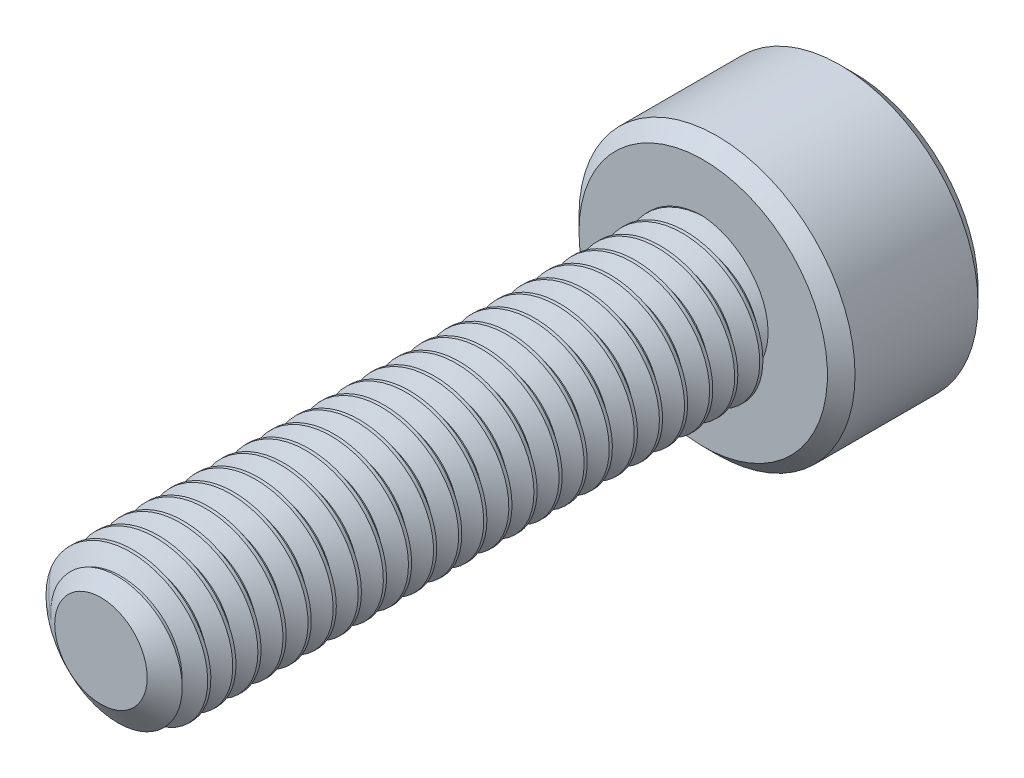
SolidWorks part; units mm, degrees
ref_plane "Front Plane" through (0, 0, 0) normal (0, 0, 1) x (1, 0, 0)
ref_plane "Top Plane" through (0, 0, 0) normal (0, 1, 0) x (1, 0, 0)
ref_plane "Right Plane" through (0, 0, 0) normal (1, 0, 0) x (0, 0, -1)
sketch "Sketch1" plane through (0, 0, 0) normal (0, 0, 1) x (1, 0, 0)
  circle A0 centre (0, 0) radius 1.5
  dimension "OD" = 3
extrude "Extrude1" add sketch "Sketch1" against normal blind 12
sketch "Sketch2" plane through (0, 0, 0) normal (0, 0, 1) x (1, 0, 0)
  circle A0 centre (0, 0) radius 1.5 construction
  circle A1 centre (0, 0) radius 1.5
curve "Helix/Spiral1" pitch 0.5 height 12.5 radius 1.5 centre (0, 0, 0) axis (0, 0, -1) start towards (0, 1, 0) parameters "pitch"=0.5
sketch "Sketch3" plane through (0, 0, 0) normal (1, 0, 0) x (0, 0, -1)
  line L0 (-0.4375, 1.5) -> (-0.25, 1.1752)
  line L1 (-0.25, 1.1752) -> (-0.1875, 1.1752)
  line L2 (-0.1875, 1.1752) -> (0, 1.5)
  line L3 (-0.4375, 1.5) -> (0, 1.5)
  line L4 (-0.2187, 1.5) -> (-0.2187, 1.1752) construction
  line L5 (-0.3438, 1.3376) -> (-0.0937, 1.3376) construction
  line L6 (0, 1.5) -> (0, -1.5) construction
  dimension "D1" = 0.0625
  dimension "D2" = 0.25
  dimension "D3" = 60
sweep "Cut-Sweep1" cut profiles "Sketch3" path "Helix/Spiral1" align with end faces yes
sketch "Sketch4" plane through (0, 0, 0) normal (1, 0, 0) x (0, 0, -1)
  line L0 (0.4053, 1.5) -> (0, 0.9212)
  line L1 (0, 0.9212) -> (0, 1.5)
  line L2 (0.4053, 1.5) -> (0, 1.5)
  line L3 (-0.4375, 1.5) -> (0, 1.5) construction
  line L4 (0, 0) -> (7.0209, 0) construction
  dimension "D1" = 55
  dimension "D2" = 0.254
revolve "Cut-Revolve1" cut sketch "Sketch4" angle 360 about L4
sketch "Sketch6" plane through (0, 0, -12) normal (0, 0, -1) x (-1, 0, 0)
  circle A0 centre (0, 0) radius 2.75
  dimension "head dia" = 5.5
extrude "Extrude2" add sketch "Sketch6" along normal blind 3
sketch "Sketch7" plane through (0, 0, -15) normal (0, 0, -1) x (-1, 0, 0)
  line L1 (0, 1.4434) -> (-1.25, 0.7217)
  line L2 (-1.25, 0.7217) -> (-1.25, -0.7217)
  line L3 (-1.25, -0.7217) -> (0, -1.4434)
  line L4 (0, -1.4434) -> (1.25, -0.7217)
  line L5 (1.25, -0.7217) -> (1.25, 0.7217)
  line L6 (1.25, 0.7217) -> (0, 1.4434)
  circle A0 centre (0, 0) radius 1.25 construction
  dimension "hex dia" = 2.5
extrude "Cut-Extrude1" cut sketch "Sketch7" against normal blind 1.875
sketch "Sketch8" plane through (0, 0, -15) normal (0, 0, -1) x (-1, 0, 0)
  circle A0 centre (0, 0) radius 1.4434
extrude "Cut-Extrude2" cut sketch "Sketch8" against normal through all draft 45
chamfer "Chamfer1" distance 0.275 angle 45 2 edges at (-2.75, 0, -15) (-2.75, 0, -12)
sketch "Sketch9" plane through (0, 0, 0) normal (1, 0, 0) x (0, 0, -1)
  line L0 (0, 1.5) -> (0, -1.5) construction
  line L1 (2.75, 1.5) -> (2.75, -1.5) construction
  dimension "D1" = 2.75
equation "\"D3@Helix/Spiral1\" = \"screw length@Extrude1\"+\"pitch@Helix/Spiral1\""
equation "\"D1@Sketch3\" = \"pitch@Helix/Spiral1\"*.125"
equation "\"D2@Sketch3\" = \"pitch@Helix/Spiral1\"*.5"
equation "\"D1@Cut-Extrude1\" = \"hex dia@Sketch7\"*.75"
equation "\"D1@Chamfer1\" = \"head dia@Sketch6\"*.05"
equation "\"D1@Sketch9\" = \"pitch@Helix/Spiral1\"*5.5"
